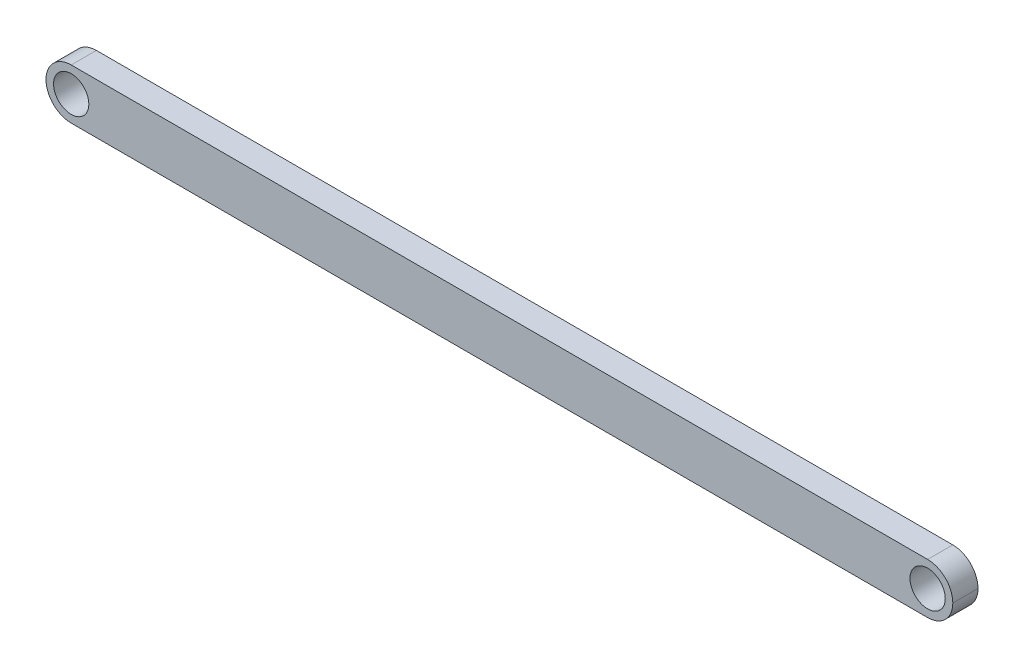
SolidWorks part; units mm, degrees
ref_plane "前视基准面" through (0, 0, 0) normal (0, 0, 1) x (1, 0, 0)
ref_plane "上视基准面" through (0, 0, 0) normal (0, 1, 0) x (1, 0, 0)
ref_plane "右视基准面" through (0, 0, 0) normal (1, 0, 0) x (0, 0, -1)
other "Configuration Table"
sketch "草图1" plane through (0, 0, 0) normal (0, 0, 1) x (1, 0, 0)
  line L1 (-180, -10) -> (180, -10)
  line L2 (-180, -10) -> (-180, 10)
  line L3 (-180, 10) -> (180, 10)
  line L4 (180, -10) -> (180, 10)
  line L5 (-180, -10) -> (180, 10) construction
  line L6 (-180, 10) -> (180, -10) construction
  circle A0 centre (-170, 0) radius 7
  circle A1 centre (170, 0) radius 7
  point P0 (0, 0)
  dimension "D3" = 14
  dimension "D4" = 14
  dimension "D1" = 20
  dimension "D2" = 360
  dimension "D5" = 170
  dimension "D6" = 170
extrude "凸台-拉伸1" add sketch "草图1" along normal blind 10
fillet "圆角1" radius 10 4 edges at (180, 10, 5) (180, -10, 5) (-180, -10, 5) (-180, 10, 5)
